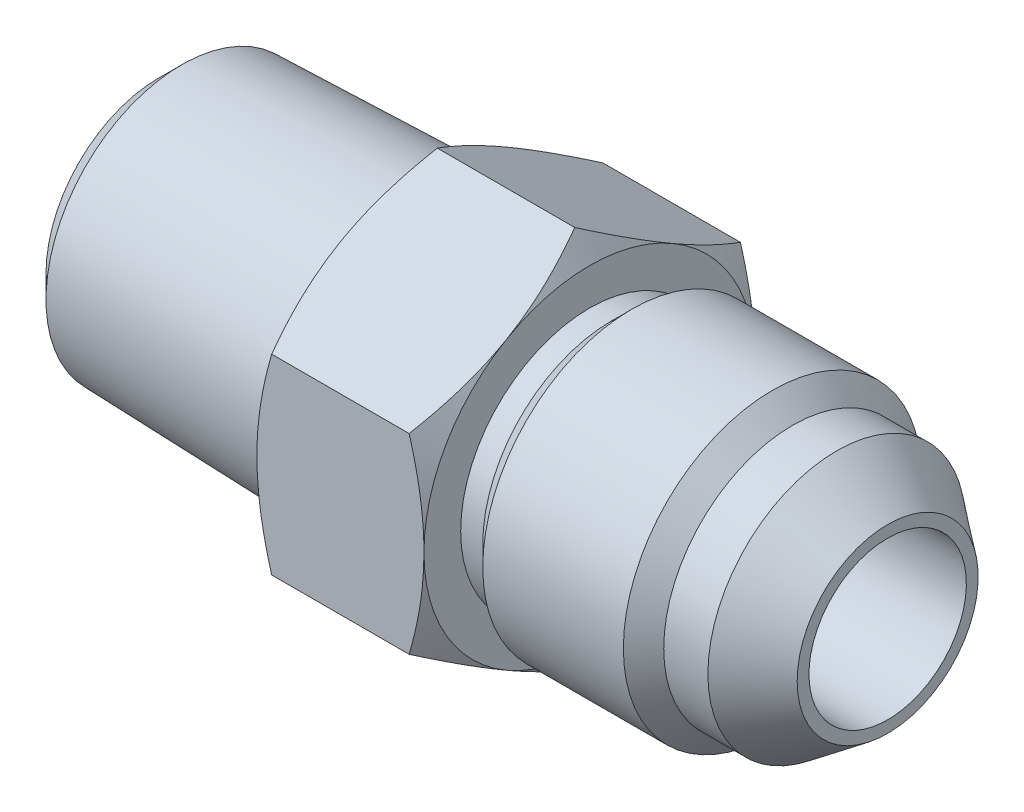
SolidWorks part; units mm, degrees
ref_plane "Front" through (0, 0, 0) normal (0, 0, 1) x (1, 0, 0)
ref_plane "Top" through (0, 0, 0) normal (0, 1, 0) x (1, 0, 0)
ref_plane "Right" through (0, 0, 0) normal (1, 0, 0) x (0, 0, -1)
sketch "Sketch6" plane through (0, 0, 0) normal (0, 0, 1) x (1, 0, 0)
  line L0 (-4.8311, 6.858) -> (-4.8311, -6.858) construction
  line L1 (17.4625, 7.1438) -> (17.4625, -7.1437) construction
  line L2 (-17.4625, 0) -> (17.4625, 0)
  line L4 (-17.4625, 0) -> (-17.4625, 7.1438)
  line L5 (-17.4625, 7.1438) -> (17.4625, 7.1438)
  line L6 (17.4625, 0) -> (17.4625, 7.1438)
  point P4 (3.175, 0)
  point P6 (-4.8311, 0)
  dimension "Straight Dia" = 14.2875
  dimension "Length" = 34.925
  dimension "L1" = 14.2875
  dimension "Pipe OD" = 13.716
  dimension "Pipe Thread Length" = 12.6314
revolve "Revolve3" add sketch "Sketch6" angle 360 about L2
sketch "Sketch14" plane through (17.4625, 0, 0) normal (-1, 0, 0) x (0, 0, 1)
  circle A1 centre (0, 0) radius 7.1438
  circle A2 centre (0, 0) radius 7.1438
  dimension "D1" = 0
curve "Helix/Spiral1" pitch 1.4111 height 15.6986 turns 11.125 parameters "Pitch"=1.4111
sketch "Sketch15" plane through (0, 0, 0) normal (0, 0, 1) x (1, 0, 0)
  line L0 (17.4625, 7.1438) -> (18.6972, 7.1438)
  line L1 (18.6972, 7.1438) -> (18.1681, 6.2272)
  line L2 (18.1681, 6.2272) -> (17.9917, 6.2272)
  line L3 (17.9917, 6.2272) -> (17.4625, 7.1438)
  line L4 (18.0799, 6.2272) -> (18.0799, 7.1438) construction
  line L5 (17.7271, 6.6855) -> (18.4326, 6.6855) construction
  dimension "D1" = 60
  dimension "D2" = 0.1764
  dimension "D3" = 0.7056
sweep "Cut-Sweep1" [suppressed] cut profiles "Sketch15" path "Helix/Spiral1"
ref_plane "Plane1" through (-4.8311, 0, 0) normal (1, 0, 0) x (0, 0, -1)
sketch "Sketch12" plane through (-4.8311, 0, 0) normal (1, 0, 0) x (0, 0, -1)
  line L1 (0, 9.1654) -> (-7.9375, 4.5827)
  line L2 (-7.9375, 4.5827) -> (-7.9375, -4.5827)
  line L3 (-7.9375, -4.5827) -> (0, -9.1654)
  line L4 (0, -9.1654) -> (7.9375, -4.5827)
  line L5 (7.9375, -4.5827) -> (7.9375, 4.5827)
  line L6 (7.9375, 4.5827) -> (0, 9.1654)
  circle A0 centre (0, 0) radius 7.9375 construction
  dimension "Hex" = 15.875
extrude "Extrude1" add sketch "Sketch12" along normal up to vertex (8.0061 mm away) up to point (3.175, 0, 0)
sketch "Sketch7" plane through (0, 0, 0) normal (0, 0, 1) x (1, 0, 0)
  line L0 (-17.4625, 0) -> (-17.4625, 3.7719)
  line L2 (-17.4625, 3.7719) -> (17.4625, 3.7719)
  line L4 (17.4625, 0) -> (17.4625, 7.1438) construction
  line L11 (17.4625, 3.7719) -> (17.4625, 0)
  line L12 (17.4625, 0) -> (-17.4625, 0)
  line L13 (-17.4625, 3.7719) -> (-17.4625, -3.7719) construction
  dimension "ID" = 7.5438
sketch "Sketch10" plane through (0, 0, 0) normal (0, 0, 1) x (1, 0, 0)
  line L0 (-17.4625, 7.1438) -> (17.4625, 7.1438) construction
  line L1 (17.4625, 7.1438) -> (18.6972, 7.1438) construction
  line L3 (3.175, 9.1654) -> (3.175, 4.5827) construction
  line L5 (0, 0) -> (-17.4625, 0) construction
  line L6 (5.2007, 7.1438) -> (3.175, 7.1438)
  line L9 (3.175, 6.1764) -> (3.175, 7.1438)
  line L21 (17.4625, 7.1438) -> (11.9384, 7.1438)
  line L22 (11.9384, 7.1438) -> (12.9058, 6.1764)
  line L23 (12.9058, 6.1764) -> (15.0224, 6.1764)
  line L24 (15.0224, 6.1764) -> (17.4625, 4.3377)
  line L25 (17.4625, 4.3377) -> (17.4625, 7.1438)
  line L26 (4.2333, 6.1764) -> (3.175, 6.1764)
  line L27 (5.2007, 7.1438) -> (4.2333, 6.1764)
  point P5 (10.0835, -7.1437)
  point P9 (-10.4026, -7.1438)
  point P24 (-10.4026, 0)
  dimension "D1" = 8.6754
  dimension "D2" = 37
  dimension "D3" = 2.1167
  dimension "D5" = 45
  dimension "D4" = 1.0583
  dimension "D6" = 2.8222
  dimension "D7" = 0.0508
revolve "Cut-Revolve6" cut sketch "Sketch10" angle 360 about L2
revolve "Cut-Revolve5" cut sketch "Sketch7" angle 360 about L12
sketch "Sketch13" plane through (0, 0, 0) normal (0, 0, 1) x (1, 0, 0)
  line L0 (-4.8311, 9.1654) -> (-4.8311, 7.9375)
  line L1 (-4.8311, 4.5827) -> (-4.8311, 9.1654) construction
  line L2 (-4.8311, 7.9375) -> (-4.1221, 9.1654)
  line L3 (-4.1221, 9.1654) -> (-4.8311, 9.1654)
  line L4 (2.4661, 9.1654) -> (3.175, 7.9375)
  line L5 (3.175, 9.1654) -> (3.175, 4.5827) construction
  line L6 (3.175, 7.9375) -> (3.175, 9.1654)
  line L7 (3.175, 9.1654) -> (2.4661, 9.1654)
  dimension "D2" = 30
revolve "Cut-Revolve7" cut sketch "Sketch13" angle 360 about L2
sketch "Sketch17" plane through (-17.4625, 0, 0) normal (-1, 0, 0) x (0, 0, 1)
  circle A0 centre (0, 0) radius 7.1438 construction
  circle A1 centre (0, 0) radius 7.1438
extrude "Cut-Extrude1" cut sketch "Sketch17" against normal up to vertex (12.6314 mm away) up to point (-4.8311, 0, 0)
ref_plane "Plane2" through (-4.8311, 0, 0) normal (1, 0, 0) x (0, 0, -1)
sketch "Sketch19" plane through (-4.8311, 0, 0) normal (1, 0, 0) x (0, 0, -1)
  circle A0 centre (0, 0) radius 6.858
extrude "Boss-Extrude1" add sketch "Sketch19" against normal up to vertex (12.6314 mm away) draft 1.75 separate body up to point (-17.4625, 0, 0)
sketch "Sketch20" plane through (-17.4625, 0, 0) normal (1, 0, 0) x (0, 0, -1)
  circle A1 centre (0, 0) radius 6.4721
  circle A2 centre (0, 0) radius 6.4721 construction
sketch "Sketch21" plane through (0, 0, 0) normal (0, 0, 1) x (1, 0, 0)
  line L0 (-18.6656, 6.352) -> (-17.5318, 6.352) construction
  line L1 (-18.8043, 6.5922) -> (-18.0987, 5.3701) construction
  line L2 (-18.2188, 5.5782) -> (-17.9786, 5.5782)
  line L3 (-18.0987, 5.3701) -> (-17.3932, 6.5922) construction
  line L4 (-18.0987, 5.3701) -> (-17.9786, 5.5782) construction
  line L5 (-18.0987, 6.352) -> (-18.0987, 6.5922) construction
  line L6 (-18.8043, 6.5922) -> (-17.3932, 6.5922) construction
  line L7 (-18.0987, 6.4721) -> (-17.4625, 6.4721) construction
  line L8 (-17.3932, 6.5922) -> (-18.7349, 6.4721)
  line L9 (-18.7349, 6.4721) -> (-18.2188, 5.5782)
  line L10 (-17.9786, 5.5782) -> (-17.3932, 6.5922)
  line L11 (-18.0987, 5.3701) -> (-18.0987, 5.5782) construction
  dimension "D2" = 0.2402
  dimension "D1" = 1.4111
curve "Helix/Spiral2" parameters "Pitch"=1.4111
chamfer "Chamfer1" distance 1.0583 angle 45 1 edges at (-17.4625, 0, -6.4721) first distance on face at (-17.4625, 0, -6.4721)
sketch "Sketch22" plane through (-4.8311, 0, 0) normal (1, 0, 0) x (0, 0, -1)
  circle A1 centre (0, 0) radius 6.858
  circle A2 centre (0, 0) radius 6.858
  dimension "D1" = 0
sweep "Cut-Sweep2" [suppressed] cut profiles "Sketch21" path "Helix/Spiral2"
extrude "Boss-Extrude3" add sketch "Sketch22" against normal up to vertex (12.6314 mm away) draft 15 up to point (-17.4625, 7.1438, 0)
combine bodies "Combine1" operation type add bodies to combine 173 169
sketch "Sketch23" plane through (-17.4625, 0, 0) normal (-1, 0, 0) x (0, 0, 1)
  circle A1 centre (0, 0) radius 4.6517
  circle A2 centre (0, 0) radius 4.6517
  dimension "D1" = 0.762
extrude "Cut-Extrude2" cut sketch "Sketch23" against normal up to vertex (12.6314 mm away) up to point (-4.8311, 0, 0)
other "CPoint1" parameters "Diameter"=9.525, "StubLength"=0
ref_axis "Axis1" through (27.4625, 0, 0) along (-1, 0, 0)
equation "\"D3@Helix/Spiral1\" = \"L1@Sketch6\"+\"Pitch@Helix/Spiral1\""
equation "\"D2@Sketch15\" = \"Pitch@Helix/Spiral1\"*.125"
equation "\"D3@Sketch15\" = \"Pitch@Helix/Spiral1\"*.5"
equation "\"D3@Sketch10\" = \"Pitch@Helix/Spiral1\"*1.5"
equation "\"D1@Sketch10\" = \"ID@Sketch7\"*1.15"
equation "\"D1@Sketch21\" = \"Pitch@Helix/Spiral2\""
equation "\"D3@Helix/Spiral2\" = \"Pipe Thread Length@Sketch6\"+\"Pitch@Helix/Spiral2\""
equation "\"D1@Chamfer1\" = \"Pitch@Helix/Spiral2\"*.75"
equation "\"D4@Sketch10\" = \"Pitch@Helix/Spiral1\"*.75"
equation "\"D6@Sketch10\" = \"Pitch@Helix/Spiral1\"*2"
